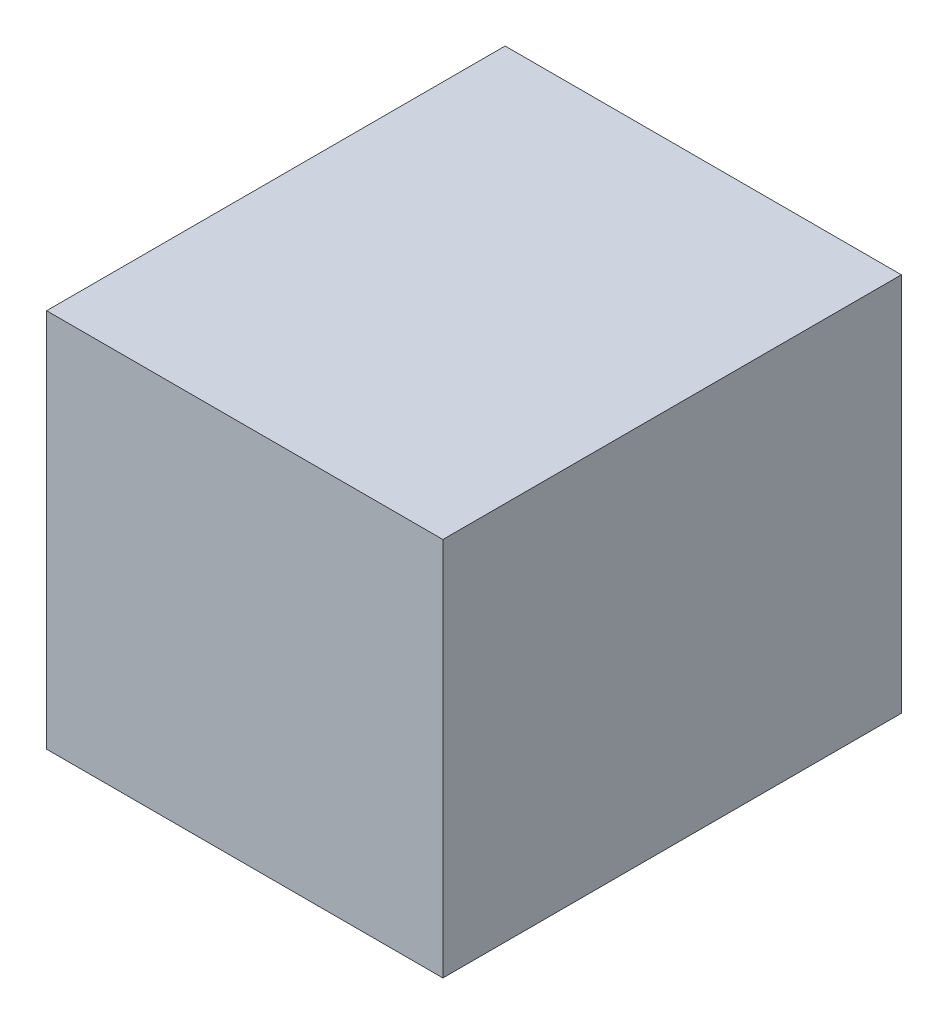
SolidWorks part; units mm, degrees
ref_plane "Front Plane" through (0, 0, 0) normal (0, 0, 1) x (1, 0, 0)
ref_plane "Top Plane" through (0, 0, 0) normal (0, 1, 0) x (1, 0, 0)
ref_plane "Right Plane" through (0, 0, 0) normal (1, 0, 0) x (0, 0, -1)
ref_axis "X-Axis" through (-88.99, 0, 0) along (1, 0, 0)
ref_axis "Y-Axis" through (0, 55, 0) along (0, -1, 0)
ref_axis "Z-Axis" through (0, 0, -88.99) along (0, 0, 1)
sketch "Sketch1" plane through (0, 0, 0) normal (0, 1, 0) x (1, 0, 0)
  line L1 (-15.6524, -18.1102) -> (15.6524, -18.1102)
  line L2 (-15.6524, -18.1102) -> (-15.6524, 18.1102)
  line L3 (-15.6524, 18.1102) -> (15.6524, 18.1102)
  line L4 (15.6524, -18.1102) -> (15.6524, 18.1102)
  line L5 (-15.6524, -18.1102) -> (15.6524, 18.1102) construction
  line L6 (-15.6524, 18.1102) -> (15.6524, -18.1102) construction
  point P0 (0, 0)
extrude "Boss-Extrude1" add sketch "Sketch1" along normal blind 30
